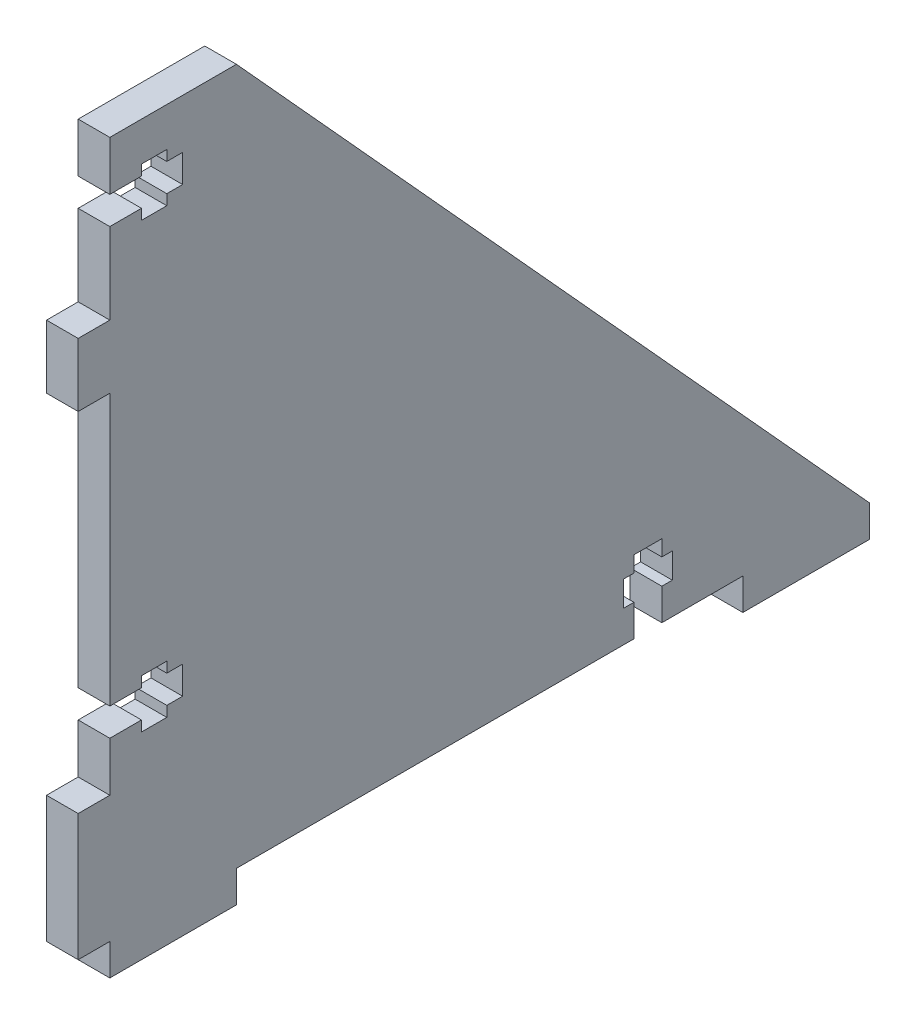
SolidWorks part; units mm, degrees
ref_plane "Front Plane" through (0, 0, 0) normal (0, 0, 1) x (1, 0, 0)
ref_plane "Top Plane" through (0, 0, 0) normal (0, 1, 0) x (1, 0, 0)
ref_plane "Right Plane" through (0, 0, 0) normal (1, 0, 0) x (0, 0, -1)
sketch "Sketch1" plane through (0, 0, 0) normal (1, 0, 0) x (0, 0, -1)
  line L0 (20, 110) -> (120, 0)
  line L1 (20, 0) -> (100, 0)
  line L2 (0, 0) -> (0, 110)
  line L3 (0, 110) -> (20, 110)
  line L5 (0, 0) -> (100, 0) construction
  line L6 (0, 97.8) -> (9, 103.85) construction
  line L7 (0, 0) -> (0, -5)
  line L8 (0, -5) -> (20, -5)
  line L9 (20, 0) -> (20, -5)
  line L10 (0, 102.2) -> (5, 102.2)
  line L11 (0, 32.2) -> (5, 32.2)
  line L12 (0, 27.8) -> (5, 27.8)
  line L13 (5, 32.2) -> (5, 27.8)
  line L14 (0, 102.2) -> (0, 97.8)
  line L15 (0, 97.8) -> (5, 97.8)
  line L16 (5, 102.2) -> (5, 97.8)
  line L17 (0, 20) -> (-5, 20)
  line L18 (0, 20) -> (0, 0)
  line L19 (0, 0) -> (-5, 0)
  line L20 (-5, 20) -> (-5, 0)
  line L21 (5, 103.85) -> (9, 103.85)
  line L22 (5, 103.85) -> (5, 96.15)
  line L23 (5, 96.15) -> (9, 96.15)
  line L24 (9, 103.85) -> (9, 96.15)
  line L25 (0, 102.2) -> (9, 96.15) construction
  line L26 (5, 96.15) -> (11.5, 102.2) construction
  line L27 (9, 102.2) -> (11.5, 102.2)
  line L28 (9, 102.2) -> (9, 97.8)
  line L29 (9, 97.8) -> (11.5, 97.8)
  line L30 (11.5, 102.2) -> (11.5, 97.8)
  line L31 (3.2727, 100) -> (9.1364, 100) construction
  line L32 (5, 103.85) -> (11.5, 97.8) construction
  line L33 (5, 33.85) -> (9, 33.85)
  line L34 (5, 33.85) -> (5, 26.15)
  line L35 (5, 26.15) -> (9, 26.15)
  line L36 (9, 33.85) -> (9, 26.15)
  line L37 (9, 32.2) -> (11.5, 32.2)
  line L38 (9, 32.2) -> (9, 27.8)
  line L39 (9, 27.8) -> (11.5, 27.8)
  line L40 (11.5, 32.2) -> (11.5, 27.8)
  line L41 (0, 27.8) -> (9, 33.85) construction
  line L42 (0, 32.2) -> (9, 26.15) construction
  line L43 (5, 26.15) -> (11.5, 32.2) construction
  line L44 (3.2727, 30) -> (9.1364, 30) construction
  line L45 (5, 33.85) -> (11.5, 27.8) construction
  line L46 (0, 102.2) -> (0, 32.2) construction
  line L47 (81.15, 9) -> (87.2, 0) construction
  line L48 (82.8, 0) -> (87.2, 0)
  line L49 (82.8, 0) -> (82.8, 5)
  line L50 (82.8, 5) -> (87.2, 5)
  line L51 (87.2, 0) -> (87.2, 5)
  line L52 (81.15, 9) -> (88.85, 9)
  line L53 (81.15, 9) -> (81.15, 5)
  line L54 (81.15, 5) -> (88.85, 5)
  line L55 (88.85, 9) -> (88.85, 5)
  line L56 (82.8, 0) -> (88.85, 9) construction
  line L57 (81.15, 5) -> (87.2, 11.5) construction
  line L58 (82.8, 11.5) -> (87.2, 11.5)
  line L59 (82.8, 11.5) -> (82.8, 9)
  line L60 (82.8, 9) -> (87.2, 9)
  line L61 (87.2, 11.5) -> (87.2, 9)
  line L62 (88.85, 5) -> (82.8, 11.5) construction
  line L63 (85, 3.2727) -> (85, 9.1364) construction
  line L65 (0, 85) -> (-5, 85)
  line L66 (0, 85) -> (0, 75)
  line L67 (0, 75) -> (-5, 75)
  line L68 (-5, 85) -> (-5, 75)
  line L69 (100, 0) -> (120, 0) construction
  line L70 (100, 0) -> (100, -5)
  line L71 (100, -5) -> (120, -5)
  line L72 (120, 0) -> (120, -5)
  dimension "D1" = 100
  dimension "D2" = 110
  dimension "D3" = 20
  dimension "D5" = 5
  dimension "D6" = 5
  dimension "D7" = 20
  dimension "D8" = 5
  dimension "D9" = 4.4
  dimension "D10" = 10
  dimension "D11" = 20
  dimension "D12" = 2
  dimension "D13" = 7.7
  dimension "D14" = 4
  dimension "D15" = 4.4
  dimension "D16" = 2.5
  dimension "D17" = 70
  dimension "D18" = 5
  dimension "D19" = 4.4
  dimension "D20" = 7.7
  dimension "D21" = 4
  dimension "D22" = 2.5
  dimension "D23" = 4.4
  dimension "D25" = 5
  dimension "D26" = 10
  dimension "D27" = 25
  dimension "D28" = 10
  dimension "D29" = 5
  dimension "D30" = 20
extrude "Boss-Extrude1" add sketch "Sketch1" along normal blind 5 contours L58 L61 L52 L55 L54 L51 L1 L0 L3 L2 L10 L22 L21 L24 L27 L30 L29 L23 L15 L11 L34 L33 L36 L37 L40 L39 L35 L12 L17 L20 L19 L7 L8 L9 L49 L53 L59 | L17 L20 L19 L2 | L65 L68 L67 L2 region at (0, 40.6675, -41.6604) region at (0, 80, 2.5) region at (0, 10, 2.5)
